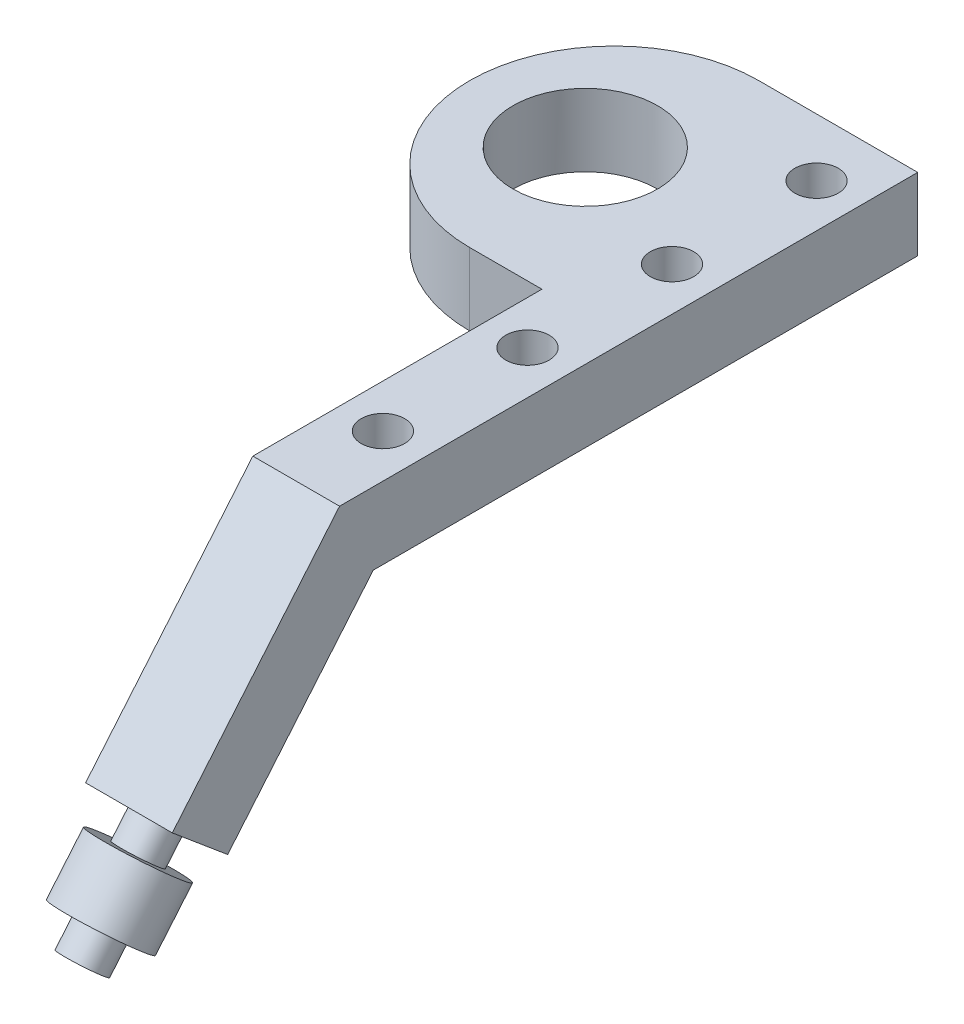
SolidWorks part; units mm, degrees
ref_plane "Front Plane" through (0, 0, 0) normal (0, 0, 1) x (1, 0, 0)
ref_plane "Top Plane" through (0, 0, 0) normal (0, 1, 0) x (1, 0, 0)
ref_plane "Right Plane" through (0, 0, 0) normal (1, 0, 0) x (0, 0, -1)
sketch "Sketch1" plane through (0, 0, 0) normal (0, 1, 0) x (1, 0, 0)
  line L1 (0, 0) -> (6, 0)
  line L2 (0, 0) -> (0, 40)
  line L3 (0, 40) -> (6, 40)
  line L4 (6, 0) -> (6, 40)
  dimension "D1" = 40
  dimension "D2" = 6
extrude "Boss-Extrude1" add sketch "Sketch1" along normal blind 5
sketch "Sketch3" plane through (0, 0, 0) normal (0, 1, 0) x (1, 0, 0)
  line L0 (0, 0) -> (6, 0) construction
  circle A0 centre (3, 6) radius 1.5
  point P2 (3, 0)
  dimension "D1" = 3
  dimension "D2" = 6
extrude "Cut-Extrude1" cut sketch "Sketch3" along normal through all
pattern_linear "LPattern1" count 4 spacing 10 along (0, 0, -1) of "Cut-Extrude1"
sketch "Sketch4" plane through (0, 0, 0) normal (1, 0, 0) x (0, 0, -1)
  line L1 (-11.5702, -8.7888) -> (-7.74, -12.0027)
  line L2 (-7.74, -12.0027) -> (3.8302, 1.7861)
  line L4 (3.8302, 1.7861) -> (0, 5)
  line L7 (0, 5) -> (-11.5702, -8.7888)
  dimension "D1" = 5
  dimension "D2" = 18
extrude "Boss-Extrude3" add sketch "Sketch4" along normal blind 6
sketch "Sketch12" plane through (0, -10.8547, 9.1082) normal (0, -0.766, 0.6428) x (1, 0, 0)
  line L1 (6, 3.2139) -> (6, -1.7861) construction
  circle A0 centre (3, 0.7139) radius 1.5
  point P4 (6, 0.7139)
  dimension "D1" = 3
  dimension "D2" = 0
extrude "Boss-Extrude7" add sketch "Sketch12" along normal blind 8
sketch "Sketch10" plane through (0, 0, 0) normal (-1, 0, 0) x (0, 0, 1)
  line L0 (-40, 0) -> (-2.3315, 0) construction
  line L1 (-40, 5) -> (-20, 5)
  line L2 (-40, 5) -> (-40, 0)
  line L3 (-40, 0) -> (-20, 0)
  line L4 (-20, 5) -> (-20, 0)
  dimension "D1" = 20
extrude "Boss-Extrude6" add sketch "Sketch10" along normal blind 15
sketch "Sketch11" plane through (0, 5, 0) normal (0, 1, 0) x (1, 0, 0)
  line L0 (-15, 20) -> (-15, 40) construction
  circle A0 centre (-7, 30) radius 5
  dimension "D1" = 10
  dimension "D2" = 8
extrude "Cut-Extrude2" cut sketch "Sketch11" against normal up to next
fillet "Fillet1" radius 10 2 edges at (-15, 2.5, -40) (-15, 2.5, -20)
sketch "Sketch14" plane through (0, -16.983, 14.2505) normal (0, -0.766, 0.6428) x (1, 0, 0)
  line L0 (1.5, 0.7139) -> (4.5, 0.7139) construction
  circle A0 centre (3, 0.7139) radius 1.5 construction
  circle A1 centre (3, 0.7139) radius 1.5 construction
sketch "Sketch15" plane through (0, -10.8547, 9.1082) normal (0, -0.766, 0.6428) x (1, 0, 0)
  line L0 (0, 0.7139) -> (6, 0.7139) construction
  line L1 (0, 3.2139) -> (0, -1.7861) construction
  line L2 (6, 3.2139) -> (6, -1.7861) construction
sketch3d "3DSketch5"
  line L0 (3, -16.5241, 14.7974) -> (3, -10.3958, 9.6551) construction
  line L1 (1.5, -16.5241, 14.7974) -> (4.5, -16.5241, 14.7974) construction
  line L2 (0, -10.3958, 9.6551) -> (6, -10.3958, 9.6551) construction
  dimension "D1" = 3
sketch3d "3DSketch6"
  line L0 (3, -16.5241, 14.7974) -> (3, -10.3958, 9.6551) construction
  circle A0 centre (3, -14.992, 13.5118) radius 3
  point P2 (3, -17.2902, 15.4402)
  dimension "D2" = 6
  dimension "D1" = 2
extrude "Boss-Extrude8" add sketch "3DSketch6" along direction (0, 0.766, -0.6428) on the side of the normal blind 4
